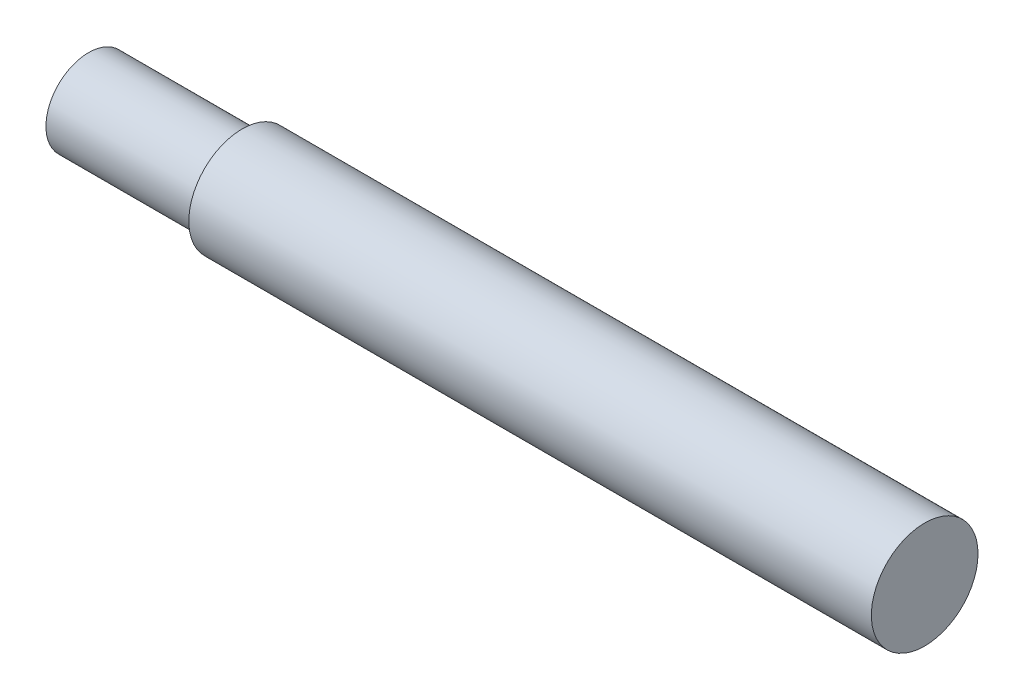
SolidWorks part; units mm, degrees
ref_plane "Front Plane" through (0, 0, 0) normal (0, 0, 1) x (1, 0, 0)
ref_plane "Top Plane" through (0, 0, 0) normal (0, 1, 0) x (1, 0, 0)
ref_plane "Right Plane" through (0, 0, 0) normal (1, 0, 0) x (0, 0, -1)
sketch "Sketch2" plane through (0, 0, 0) normal (1, 0, 0) x (0, 0, -1)
  circle A0 centre (0, 0) radius 3.9688
  dimension "D1" = 7.9375
extrude "Boss-Extrude1" add sketch "Sketch2" along normal blind 50.8
sketch "Sketch3" plane through (0, 0, 0) normal (1, 0, 0) x (0, 0, -1)
  circle A0 centre (0, 0) radius 3.175
  dimension "D1" = 6.35
extrude "Boss-Extrude2" add sketch "Sketch3" against normal blind 11.43
